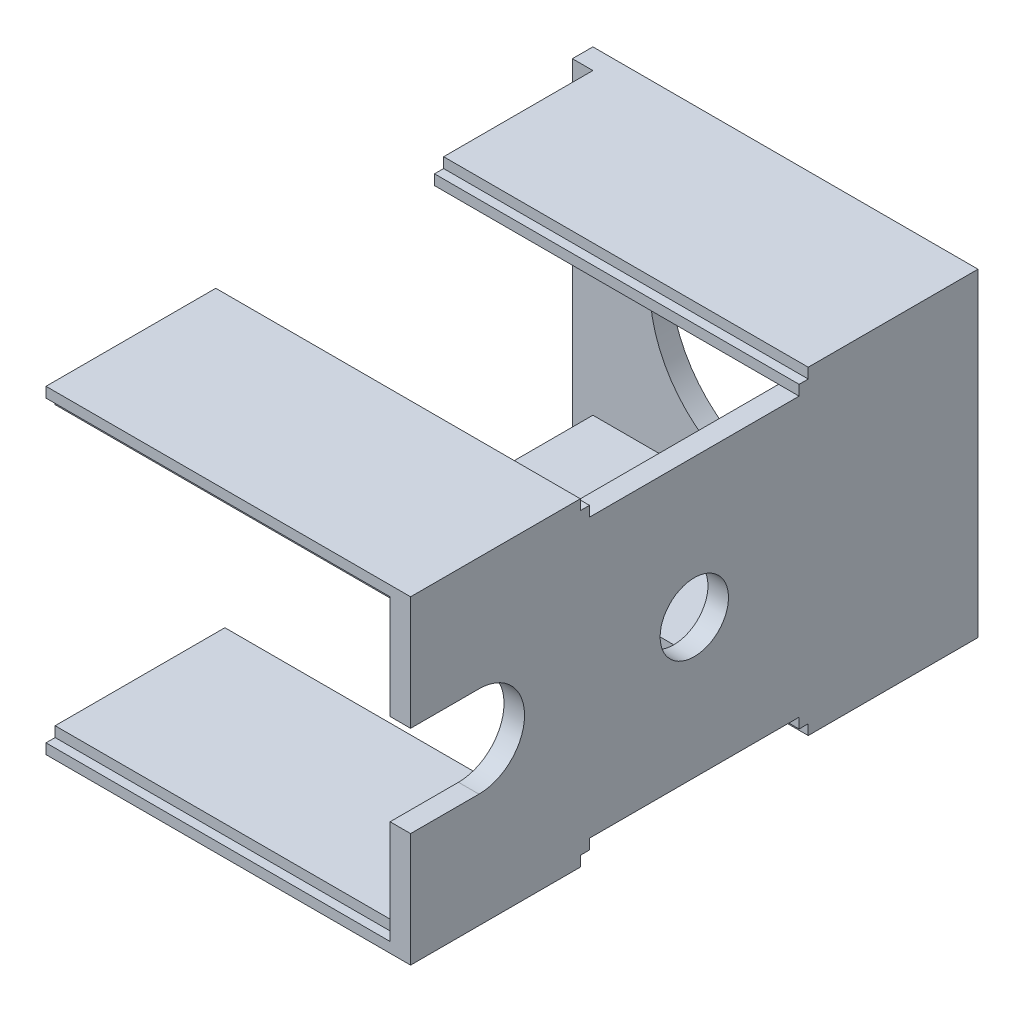
SolidWorks part; units mm, degrees
ref_plane "Front Plane" through (0, 0, 0) normal (1, 0, 0) x (0, 1, 0)
ref_plane "Top Plane" through (0, 0, 0) normal (0, 0, 1) x (0, 1, 0)
ref_plane "Right Plane" through (0, 0, 0) normal (0, 1, 0) x (-1, 0, 0)
sketch "Sketch1" plane through (0, 0, 0) normal (0, 0, 1) x (0, 1, 0)
  line L1 (-35, -40) -> (35, -40)
  line L2 (-35, -40) -> (-35, 40)
  line L3 (-35, 40) -> (35, 40)
  line L4 (35, -40) -> (35, 40)
  line L5 (-35, -40) -> (35, 40) construction
  line L6 (-35, 40) -> (35, -40) construction
  point P0 (0, 0)
  dimension "D1" = 70
  dimension "D2" = 80
extrude "Boss-Extrude1" add sketch "Sketch1" along normal blind 4.5
sketch "Sketch2" plane through (0, 0, 4.5) normal (0, 0, 1) x (1, 0, 0)
  line L0 (40, 35) -> (-40, 35) construction
  line L1 (40, -35) -> (35.5, -35)
  line L2 (40, -35) -> (40, 35)
  line L3 (40, 35) -> (35.5, 35)
  line L4 (35.5, -35) -> (35.5, 35)
  dimension "D1" = 4.5
extrude "Boss-Extrude2" add sketch "Sketch2" along normal blind 120
sketch "Sketch3" plane through (0, 0, 4.5) normal (0, 0, 1) x (1, 0, 0)
  line L0 (35.5, 35) -> (-40, 35)
  line L2 (-40, -35) -> (35.5, -35)
  line L3 (35.5, -35) -> (35.5, -30.5)
  line L4 (35.5, 35) -> (35.5, -35) construction
  line L5 (35.5, -30.5) -> (-40, -30.5)
  line L7 (-40, 30.5) -> (35.5, 30.5)
  line L8 (35.5, 30.5) -> (35.5, 35)
  line L9 (-40, 35) -> (-40, -35) construction
  line L10 (-40, 35) -> (-40, 30.5)
  line L11 (-40, -30.5) -> (-40, -35)
  dimension "D1" = 4.5
extrude "Boss-Extrude3" add sketch "Sketch3" along normal blind 120
sketch "Sketch4" plane through (0, 0, 0) normal (0, 0, -1) x (1, 0, 0)
  circle A0 centre (0, 0) radius 27.5
  dimension "D1" = 55
extrude "Cut-Extrude1" cut sketch "Sketch4" against normal up to next
sketch "Sketch5" plane through (35.5, 0, 0) normal (-1, 0, 0) x (0, -1, 0)
  line L0 (0, 124.5) -> (0, 0) construction
  line L1 (-30.5, 124.5) -> (30.5, 124.5) construction
  line L3 (-10, 124.5) -> (10, 124.5)
  line L4 (10, 124.5) -> (10, 109.5)
  line L5 (-10, 109.5) -> (-10, 124.5)
  line L6 (-35, 0) -> (35, 0) construction
  arc A0 (10, 109.5) -> (-10, 109.5) centre (0, 109.5) cw
  circle A1 centre (0, 62.25) radius 7.5
  dimension "D2" = 15
  dimension "D3" = 15
  dimension "D1" = 20
extrude "Cut-Extrude2" cut sketch "Sketch5" against normal up to next
sketch "Sketch7" plane through (-40, 0, 0) normal (-1, 0, 0) x (0, -1, 0)
  line L0 (-30.5, 85.25) -> (-32.75, 85.25)
  line L1 (-30.5, 124.5) -> (-30.5, 4.5) construction
  line L2 (-32.75, 85.25) -> (-32.75, 87.25)
  line L3 (-32.75, 87.25) -> (-35, 87.25)
  line L4 (-35, 124.5) -> (-35, 0) construction
  line L5 (-35, 87.25) -> (-35, 37.25)
  line L6 (-35, 37.25) -> (-32.75, 37.25)
  line L7 (-32.75, 37.25) -> (-32.75, 39.25)
  line L8 (-32.75, 39.25) -> (-30.5, 39.25)
  line L9 (-30.5, 124.5) -> (-30.5, 4.5) construction
  line L10 (-30.5, 39.25) -> (-30.5, 85.25)
  line L11 (-35, 62.25) -> (-30.5, 62.25) construction
  line L12 (0, 0) -> (0, 4.5) construction
  line L13 (-30.5, 4.5) -> (30.5, 4.5) construction
  line L14 (32.75, 39.25) -> (30.5, 39.25)
  line L15 (32.75, 37.25) -> (32.75, 39.25)
  line L16 (35, 37.25) -> (32.75, 37.25)
  line L17 (35, 87.25) -> (35, 37.25)
  line L18 (32.75, 87.25) -> (35, 87.25)
  line L19 (32.75, 85.25) -> (32.75, 87.25)
  line L20 (30.5, 85.25) -> (32.75, 85.25)
  line L21 (30.5, 39.25) -> (30.5, 85.25)
  dimension "D1" = 2.25
  dimension "D2" = 2
  dimension "D3" = 50
extrude "Cut-Extrude3" cut sketch "Sketch7" against normal through all
sketch "Sketch8" plane through (-40, 0, 0) normal (-1, 0, 0) x (0, -1, 0)
  line L1 (-30.5, 124.5) -> (-32.75, 124.5)
  line L2 (-30.5, 124.5) -> (-30.5, 122.5)
  line L3 (-30.5, 122.5) -> (-32.75, 122.5)
  line L4 (-32.75, 124.5) -> (-32.75, 122.5)
  line L5 (30.5, 124.5) -> (32.75, 124.5)
  line L6 (30.5, 124.5) -> (30.5, 122.5)
  line L7 (30.5, 122.5) -> (32.75, 122.5)
  line L8 (32.75, 124.5) -> (32.75, 122.5)
  dimension "D1" = 2.25
  dimension "D2" = 2
  dimension "D3" = 2
  dimension "D4" = 2.25
extrude "Cut-Extrude4" cut sketch "Sketch8" against normal up to surface (75.5 mm away) up to face at (35.5, -7.5, 62.25)
sketch "Sketch9" plane through (-40, 0, 0) normal (-1, 0, 0) x (0, -1, 0)
  line L0 (35, 37.25) -> (35, 0) construction
  line L1 (-35, 0) -> (35, 0)
  line L2 (-35, 0) -> (-35, 4.5)
  line L3 (-35, 4.5) -> (35, 4.5)
  line L4 (35, 0) -> (35, 4.5)
  line L5 (-30.5, 4.5) -> (30.5, 4.5) construction
extrude "Boss-Extrude5" add sketch "Sketch9" along normal blind 4.5
